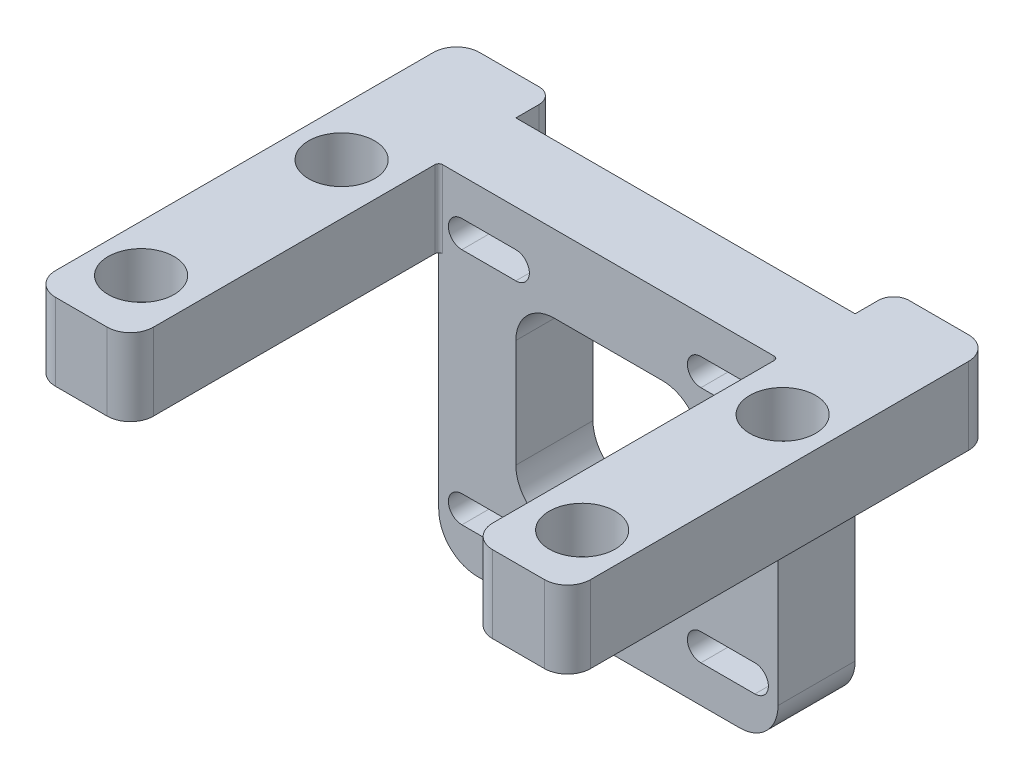
SolidWorks part; units mm, degrees
ref_plane "Front Plane" through (0, 0, 0) normal (0, 0, 1) x (1, 0, 0)
ref_plane "Top Plane" through (0, 0, 0) normal (0, 1, 0) x (1, 0, 0)
ref_plane "Right Plane" through (0, 0, 0) normal (1, 0, 0) x (0, 0, -1)
sketch "Sketch1" plane through (0, 0, 0) normal (0, 0, 1) x (1, 0, 0)
  line L0 (-19, 15.45) -> (-10.25, 15.45) construction
  line L1 (-22, 22) -> (22, 22)
  line L2 (-22, 22) -> (-22, -22)
  line L3 (-22, -22) -> (22, -22)
  line L4 (22, 22) -> (22, -22)
  line L5 (-22, 22) -> (22, -22) construction
  line L6 (-22, -22) -> (22, 22) construction
  line L7 (7, 12) -> (-7, 12)
  line L8 (12, 7) -> (12, -7)
  line L9 (7, -12) -> (-7, -12)
  line L10 (-12, 7) -> (-12, -7)
  line L11 (12, 12) -> (-12, -12) construction
  line L12 (12, -12) -> (-12, 12) construction
  line L13 (-19, 17.2) -> (-12, 17.2)
  line L14 (-19, 13.7) -> (-12, 13.7)
  line L15 (0, 0) -> (50000, 0) construction
  line L16 (-19, -17.2) -> (-12, -17.2)
  line L19 (12, 17.2) -> (19, 17.2)
  line L20 (12, 13.7) -> (19, 13.7)
  line L21 (10.25, 15.45) -> (19, 15.45) construction
  line L22 (-19, -13.7) -> (-12, -13.7)
  line L23 (12, -13.7) -> (19, -13.7)
  line L24 (12, -17.2) -> (19, -17.2)
  arc A0 (-12, -7) -> (-7, -12) centre (-7, -7) ccw
  arc A1 (7, -12) -> (12, -7) centre (7, -7) ccw
  arc A2 (12, 7) -> (7, 12) centre (7, 7) ccw
  arc A3 (-7, 12) -> (-12, 7) centre (-7, 7) ccw
  arc A4 (-19, 17.2) -> (-19, 13.7) centre (-19, 15.45) ccw
  arc A5 (19, 13.7) -> (19, 17.2) centre (19, 15.45) ccw
  circle A8 centre (0, 0) radius 12 construction
  arc A9 (12, 17.2) -> (12, 13.7) centre (12, 15.45) ccw
  arc A10 (-12, 17.2) -> (-12, 13.7) centre (-12, 15.45) cw
  arc A11 (-19, -17.2) -> (-19, -13.7) centre (-19, -15.45) cw
  arc A12 (-12, -17.2) -> (-12, -13.7) centre (-12, -15.45) ccw
  arc A13 (12, -17.2) -> (12, -13.7) centre (12, -15.45) cw
  arc A14 (19, -13.7) -> (19, -17.2) centre (19, -15.45) cw
  point P0 (0, 0)
  point P6 (0, 0)
  dimension "D4" = 5
  dimension "D9" = 1.75
  dimension "D1" = 44
  dimension "D2" = 44
  dimension "D3" = 24
  dimension "D5" = 38
  dimension "D6" = 1.75
  dimension "D7" = 15.45
  dimension "D8" = 7
extrude "Boss-Extrude1" add sketch "Sketch1" along normal blind 10
sketch "Sketch2" plane through (22, 0, 0) normal (1, 0, 0) x (0, 0, -1)
  line L0 (5, 12) -> (-50, 12)
  line L2 (5, 12) -> (5, 22)
  line L4 (-50, 12) -> (-50, 16)
  line L5 (-50, 16) -> (-15.3222, 16) construction
  line L6 (5, 22) -> (-50, 22)
  line L7 (-50, 22) -> (-50, 16)
  line L8 (-10, 22) -> (0, 22) construction
  line L12 (0, -22) -> (0, 22) construction
  dimension "D4" = 5
  dimension "D1" = 4
  dimension "D2" = 55
  dimension "D3" = 12
extrude "Boss-Extrude2" add sketch "Sketch2" along normal blind 12.7
sketch "Sketch3" plane through (0, 12, 0) normal (0, -1, 0) x (1, 0, 0)
  line L1 (34.7, 50) -> (34.7, -5) construction
  circle A0 centre (28.6, 42) radius 2.6
  circle A1 centre (28.6, 16) radius 2.6
  dimension "D2" = 5.2
  dimension "D1" = 6.1
  dimension "D3" = 8
  dimension "D4" = 26
extrude "Cut-Extrude1" cut sketch "Sketch3" against normal through all
ref_plane "Plane1" through (0, 16, 0) normal (0, -1, 0) x (-1, 0, 0)
sketch "Sketch4" plane through (0, 16, 0) normal (0, -1, 0) x (-1, 0, 0)
  circle A0 centre (-28.6, -16) radius 4.275
  circle A1 centre (-28.6, -42) radius 4.275
  dimension "D1" = 8.55
  dimension "D2" = 8.55
extrude "Cut-Extrude2" cut sketch "Sketch4" against normal through all
ref_plane "Plane2" through (0, 0, 0) normal (1, 0, 0) x (0, 0, -1)
mirror "Mirror1" about plane through (0, 0, 0) normal (1, 0, 0) of "Cut-Extrude1", "Boss-Extrude2", "Cut-Extrude2"
fillet "Fillet1" radius 3 6 edges at (34.7, 17, -5) (-34.7, 17, -5) (34.7, 17, 50) (22, 17, 50) (-22, 17, 50) (-34.7, 17, 50)
fillet "Fillet2" radius 5 2 edges at (22, -22, 5) (-22, -22, 5)
fillet "Fillet3" radius 0.5 2 edges at (-22, 17, 10) (22, 17, 10)
fillet "Fillet4" radius 2 2 edges at (22, 17, -5) (-22, 17, -5)
